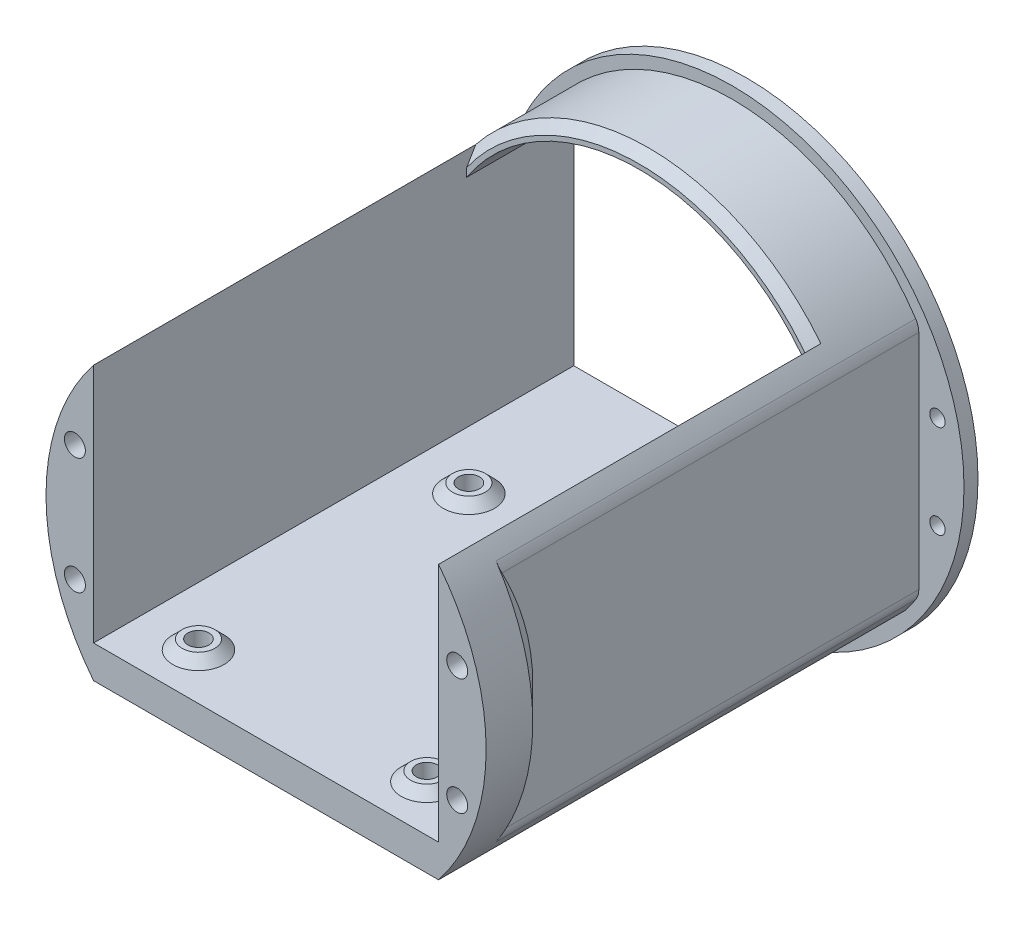
SolidWorks part; units mm, degrees
ref_plane "Front Plane" through (0, 0, 0) normal (0, 0, 1) x (1, 0, 0)
ref_plane "Top Plane" through (0, 0, 0) normal (0, 1, 0) x (1, 0, 0)
ref_plane "Right Plane" through (0, 0, 0) normal (1, 0, 0) x (0, 0, -1)
sketch "Sketch1" plane through (0, 0, 0) normal (0, 0, 1) x (1, 0, 0)
  line L0 (-40, 78.8797) -> (-40, 31.1203) construction
  line L1 (40, 31.1203) -> (40, 78.8797) construction
  line L2 (-40, 78.8797) -> (-40, 31.1203)
  line L3 (40, 31.1203) -> (40, 78.8797)
  circle A0 centre (-44, 45) radius 2.25 construction
  circle A2 centre (0, 55) radius 49.7
  circle A3 centre (0, 55) radius 49.7
  circle A7 centre (44, 45) radius 1.65
  circle A8 centre (44, 65) radius 1.65
  circle A9 centre (-44, 65) radius 1.65
  circle A10 centre (-44, 45) radius 1.65
  arc A11 (-39.3333, 81.0908) -> (-40, 78.8797) centre (-36, 78.8797) ccw construction
  arc A12 (-40, 31.1203) -> (-39.3333, 28.9092) centre (-36, 31.1203) ccw construction
  arc A13 (-39.3333, 28.9092) -> (39.3333, 28.9092) centre (0, 55) ccw construction
  arc A14 (39.3333, 28.9092) -> (40, 31.1203) centre (36, 31.1203) ccw construction
  arc A15 (40, 78.8797) -> (39.3333, 81.0908) centre (36, 78.8797) ccw construction
  arc A16 (39.3333, 81.0908) -> (-39.3333, 81.0908) centre (0, 55) ccw construction
  arc A17 (-39.3333, 81.0908) -> (-40, 78.8797) centre (-36, 78.8797) ccw
  arc A18 (-40, 31.1203) -> (-39.3333, 28.9092) centre (-36, 31.1203) ccw
  arc A19 (-39.3333, 28.9092) -> (39.3333, 28.9092) centre (0, 55) ccw
  arc A20 (39.3333, 28.9092) -> (40, 31.1203) centre (36, 31.1203) ccw
  arc A21 (40, 78.8797) -> (39.3333, 81.0908) centre (36, 78.8797) ccw
  arc A22 (39.3333, 81.0908) -> (-39.3333, 81.0908) centre (0, 55) ccw
  circle A24 centre (-44, 65) radius 2.25 construction
  circle A25 centre (44, 65) radius 2.25 construction
  circle A26 centre (44, 45) radius 2.25 construction
  dimension "D2" = 3.3
  dimension "D1" = 0.5
extrude "Boss-Extrude1" add sketch "Sketch1" along normal mid plane 3
sketch "Sketch3" plane through (0, 0, 1.5) normal (0, 0, 1) x (1, 0, 0)
  line L0 (-37, 84.306) -> (-37, 32.694)
  line L1 (37, 84.306) -> (37, 32.694)
  line L3 (40, 31.1203) -> (40, 78.8797) construction
  line L4 (-40, 78.8797) -> (-40, 31.1203) construction
  line L5 (40, 31.1203) -> (40, 78.8797)
  line L6 (-40, 78.8797) -> (-40, 31.1203)
  line L8 (-37, 25.694) -> (37, 25.694)
  line L10 (-37, 32.694) -> (37, 32.694)
  circle A0 centre (-44, 65) radius 3.5 construction
  arc A1 (39.3333, 81.0908) -> (-39.3333, 81.0908) centre (0, 55) ccw construction
  circle A2 centre (-44, 45) radius 3.5 construction
  circle A3 centre (44, 45) radius 3.5 construction
  circle A4 centre (44, 65) radius 3.5 construction
  arc A5 (-39.3333, 28.9092) -> (39.3333, 28.9092) centre (0, 55) ccw construction
  arc A6 (40, 78.8797) -> (39.3333, 81.0908) centre (36, 78.8797) ccw construction
  arc A7 (39.3333, 28.9092) -> (40, 31.1203) centre (36, 31.1203) ccw construction
  arc A8 (-40, 31.1203) -> (-39.3333, 28.9092) centre (-36, 31.1203) ccw construction
  arc A9 (-39.3333, 81.0908) -> (-40, 78.8797) centre (-36, 78.8797) ccw construction
  arc A10 (40, 78.8797) -> (39.3333, 81.0908) centre (36, 78.8797) ccw
  arc A11 (39.3333, 28.9092) -> (40, 31.1203) centre (36, 31.1203) ccw
  arc A12 (-39.3333, 28.9092) -> (-37, 25.694) centre (0, 55) ccw
  arc A13 (-40, 31.1203) -> (-39.3333, 28.9092) centre (-36, 31.1203) ccw
  arc A14 (-39.3333, 81.0908) -> (-40, 78.8797) centre (-36, 78.8797) ccw
  arc A15 (39.3333, 81.0908) -> (37, 84.306) centre (0, 55) ccw
  arc A16 (-37, 84.306) -> (-39.3333, 81.0908) centre (0, 55) ccw
  arc A17 (37, 25.694) -> (39.3333, 28.9092) centre (0, 55) ccw
  dimension "D1" = 7
  dimension "D2" = 3
  dimension "D3" = 3
  dimension "D4" = 7
extrude "Boss-Extrude2" add sketch "Sketch3" along normal blind 100 and the other way blind 3
sketch "Sketch4" plane through (0, 32.694, 0) normal (0, 1, 0) x (1, 0, 0)
  line L0 (0, 1.5) -> (0, -91.5) construction
  line L1 (37, 1.5) -> (-37, 1.5) construction
  line L2 (-24.5, -91.5) -> (24.5, -91.5) construction
  line L3 (-24.5, -33.5) -> (24.5, -33.5) construction
  line L4 (37, -101.5) -> (-37, -101.5) construction
  circle A0 centre (-24.5, -91.5) radius 2.25
  circle A1 centre (-24.5, -33.5) radius 2.25
  circle A2 centre (24.5, -33.5) radius 2.25
  circle A3 centre (24.5, -91.5) radius 2.25
  point P7 (0, -91.5)
  point P10 (0, -33.5)
  dimension "D4" = 4.5
  dimension "D1" = 49
  dimension "D2" = 58
  dimension "D3" = 10
extrude "Cut-Extrude1" cut sketch "Sketch4" against normal through all
sketch "Sketch5" plane through (0, 32.694, 0) normal (0, 1, 0) x (1, 0, 0)
  circle A0 centre (-24.5, -33.5) radius 3.5
  circle A1 centre (24.5, -33.5) radius 3.5
  circle A2 centre (24.5, -91.5) radius 3.5
  circle A3 centre (-24.5, -91.5) radius 3.5
  circle A4 centre (24.5, -33.5) radius 2.25 construction
  circle A5 centre (24.5, -91.5) radius 2.25 construction
  circle A6 centre (-24.5, -91.5) radius 2.25 construction
  circle A7 centre (-24.5, -33.5) radius 2.25 construction
  circle A8 centre (24.5, -33.5) radius 2.25
  circle A9 centre (24.5, -91.5) radius 2.25
  circle A10 centre (-24.5, -91.5) radius 2.25
  circle A11 centre (-24.5, -33.5) radius 2.25
  dimension "D1" = 7
extrude "Boss-Extrude3" add sketch "Sketch5" along normal blind 2
chamfer "Chamfer1" distance 2 angle 45 4 edges at (-24.5, 32.694, 95) (24.5, 32.694, 95) (24.5, 32.694, 37) (-24.5, 32.694, 37)
sketch "Sketch6" plane through (0, 0, 101.5) normal (0, 0, 1) x (1, 0, 0)
  line L0 (40, 31.1203) -> (40, 78.8797) construction
  line L1 (-40, 78.8797) -> (-40, 31.1203) construction
  line L2 (40, 31.1203) -> (40, 78.8797)
  line L3 (-40, 78.8797) -> (-40, 31.1203)
  arc A0 (-39.3333, 81.0908) -> (-39.3333, 28.9092) centre (0, 55) ccw
  circle A1 centre (0, 55) radius 49.7 construction
  arc A2 (-37, 25.694) -> (37, 25.694) centre (0, 55) ccw construction
  arc A3 (40, 78.8797) -> (39.3333, 81.0908) centre (36, 78.8797) ccw construction
  arc A4 (39.3333, 28.9092) -> (40, 31.1203) centre (36, 31.1203) ccw construction
  arc A5 (-40, 31.1203) -> (-39.3333, 28.9092) centre (-36, 31.1203) ccw construction
  arc A6 (-39.3333, 81.0908) -> (-40, 78.8797) centre (-36, 78.8797) ccw construction
  arc A7 (40, 78.8797) -> (39.3333, 81.0908) centre (36, 78.8797) ccw
  arc A8 (39.3333, 28.9092) -> (40, 31.1203) centre (36, 31.1203) ccw
  arc A9 (-40, 31.1203) -> (-39.3333, 28.9092) centre (-36, 31.1203) ccw
  arc A10 (-39.3333, 81.0908) -> (-40, 78.8797) centre (-36, 78.8797) ccw
  arc A11 (39.3333, 28.9092) -> (39.3333, 81.0908) centre (0, 55) ccw
extrude "Boss-Extrude4" add sketch "Sketch6" against normal blind 20
chamfer "Chamfer2" distance 10 angle 45 2 edges at (-47.2, 55, 81.5) (47.2, 55, 81.5)
sketch "Sketch7" plane through (0, 0, 101.5) normal (0, 0, 1) x (1, 0, 0)
  line L1 (41, 67.5) -> (-41, 67.5) construction
  line L2 (41, 67.5) -> (41, 42.5) construction
  line L3 (41, 42.5) -> (-41, 42.5) construction
  line L4 (-41, 67.5) -> (-41, 42.5) construction
  line L5 (41, 67.5) -> (-41, 42.5) construction
  line L6 (41, 42.5) -> (-41, 67.5) construction
  circle A0 centre (0, 55) radius 49.7 construction
  circle A1 centre (-41, 67.5) radius 2.25
  circle A2 centre (41, 67.5) radius 2.25
  circle A3 centre (41, 42.5) radius 2.25
  circle A4 centre (-41, 42.5) radius 2.25
  point P0 (0, 55)
  dimension "D3" = 4.5
  dimension "D1" = 82
  dimension "D2" = 25
extrude "Cut-Extrude2" cut sketch "Sketch7" against normal blind 10
sketch "Sketch8" plane through (0, 0, -1.5) normal (0, 0, -1) x (-1, 0, 0)
  line L0 (37, 25.694) -> (-37, 25.694) construction
  line L1 (37, 25.694) -> (-37, 25.694)
  arc A0 (-37, 25.694) -> (37, 25.694) centre (0, 55) ccw construction
  arc A1 (-37, 25.694) -> (37, 25.694) centre (0, 55) ccw
extrude "Boss-Extrude5" add sketch "Sketch8" against normal up to surface (3 mm away) up to face at (-42.35, 65, 1.5)
sketch "Sketch10" plane through (0, 0, 1.5) normal (0, 0, 1) x (1, 0, 0)
  line L0 (-37, 84.306) -> (-37, 79.1793)
  line L1 (37, 84.306) -> (37, 79.1793)
  arc A0 (37, 79.1793) -> (-37, 79.1793) centre (0, 55) ccw
  arc A1 (37, 84.306) -> (-37, 84.306) centre (0, 55) ccw construction
  arc A2 (37, 84.306) -> (-37, 84.306) centre (0, 55) ccw
  dimension "D1" = 3
extrude "Boss-Extrude6" add sketch "Sketch10" along normal blind 20 and the other way blind 3
chamfer "Chamfer3" distance 2 angle 45 1 edges at (0, 102.2, 21.5)
